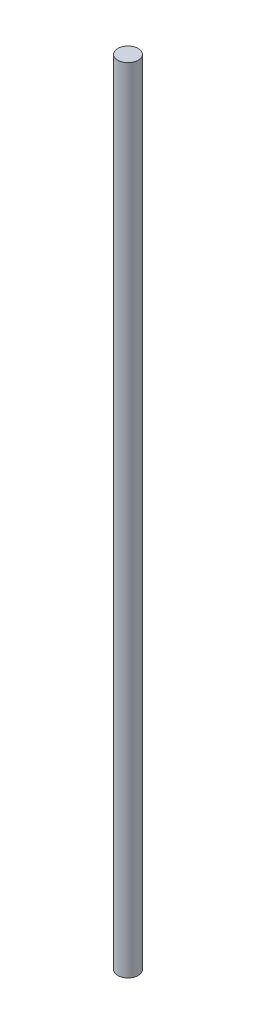
SolidWorks part; units mm, degrees
material "Hexcel AS4C (3000 Filaments)"
ref_plane "Front Plane" through (0, 0, 0) normal (0, 0, 1) x (1, 0, 0)
ref_plane "Top Plane" through (0, 0, 0) normal (0, 1, 0) x (1, 0, 0)
ref_plane "Right Plane" through (0, 0, 0) normal (1, 0, 0) x (0, 0, -1)
sketch "Sketch1" plane through (0, 0, 0) normal (0, 1, 0) x (1, 0, 0)
  circle A0 centre (0, 0) radius 2
  dimension "D1" = 4
extrude "Boss-Extrude1" add sketch "Sketch1" along normal blind 155
